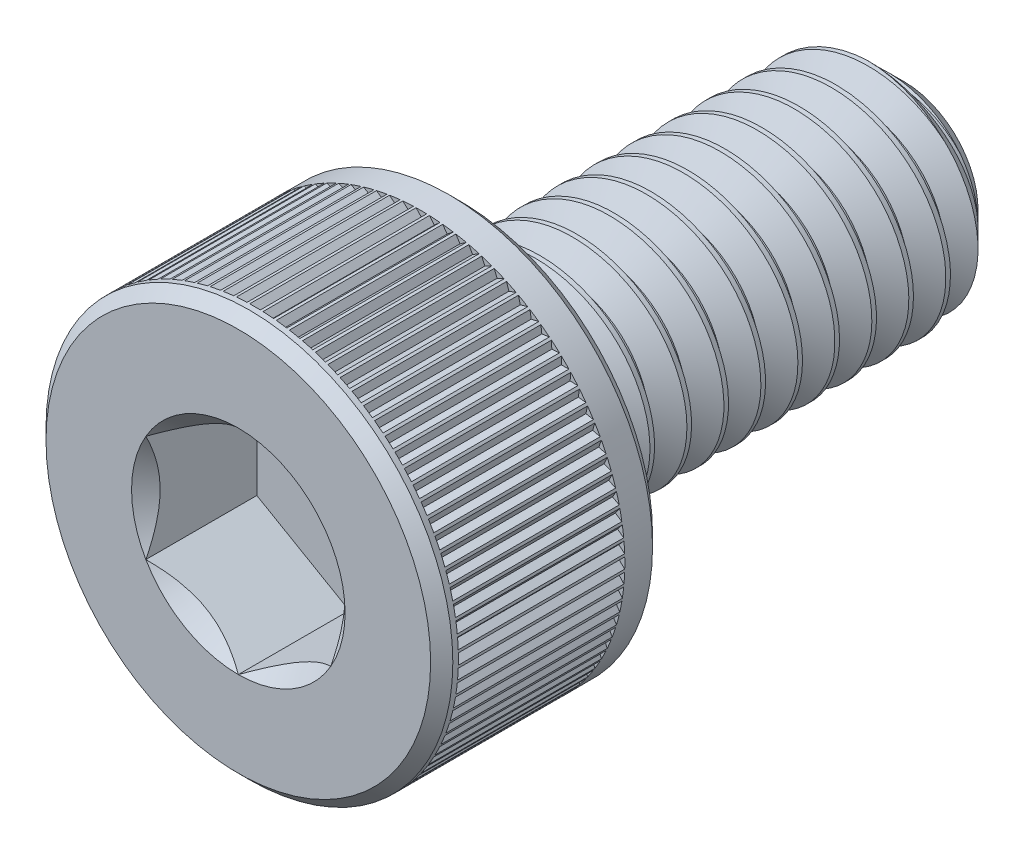
SolidWorks part; units mm, degrees
ref_plane "Front Plane" through (0, 0, 0) normal (0, 0, 1) x (1, 0, 0)
ref_plane "Top Plane" through (0, 0, 0) normal (0, 1, 0) x (1, 0, 0)
ref_plane "Right Plane" through (0, 0, 0) normal (1, 0, 0) x (0, 0, -1)
sketch "Sketch1" plane through (0, 0, 0) normal (1, 0, 0) x (0, 0, -1)
  line L0 (-4.5, 0) -> (4.5, 0) construction
  line L1 (4.5, 0) -> (4.5, 1) construction
  line L2 (4.5, 1) -> (4, 1.5) construction
  line L3 (4, 1.5) -> (-1.5, 1.5) construction
  line L5 (-1.5, 1.5) -> (-1.5, 2.75) construction
  line L6 (-1.5, 2.75) -> (-4.5, 2.75) construction
  line L7 (-4.5, 2.75) -> (-4.5, 0) construction
  line L8 (4.5, 1) -> (4.5, 1.5) construction
  line L9 (4.4687, 1.5541) -> (4.7187, 1.1211) construction
  line L10 (4.7187, 1.1211) -> (4.9687, 1.5541) construction
  line L11 (4.9687, 1.5541) -> (4.4687, 1.5541) construction
  line L12 (4.7188, 1.5541) -> (4.7188, 1.5) construction
  line L13 (4.7187, 1.1211) -> (4.7187, 1.1752) construction
  line L14 (4.6875, 1.1752) -> (4.75, 1.1752) construction
  line L15 (4.5, 1.5) -> (4.9375, 1.5) construction
  line L16 (4.4844, 1.5271) -> (4.9531, 1.5271) construction
  line L17 (4.5, 0) -> (4.5, -1.5) construction
  line L18 (-1.65, 2.75) -> (-1.5, 2.6) construction
  line L19 (-4.35, 2.75) -> (-4.5, 2.6) construction
  point P0 (-4.5, 1.25)
  point P3 (2.75, 1.5)
  point P4 (0, 0)
  point P22 (4.7187, 1.1752)
  point P24 (-1.5, 1.5)
  point P25 (4.7188, 1.5)
  point P28 (4.7188, 1.5271)
  point P29 (2.75, -1.5)
  point P31 (-3, 2.75)
  point P37 (-2.025, 2.75)
  point P38 (-4.275, 2.75)
  point P41 (-3, 0)
  dimension "head height" = 3
  dimension "D1" = 45
  dimension "Head Diameter" = 5.5
  dimension "Thread Size" = 3
  dimension "drive size" = 2.5
  dimension "Thread Pitch" = 0.5
  dimension "D2" = 0.0625
  dimension "D3" = 0.5
  dimension "D4" = 1.75
  dimension "D7" = 0.15
  dimension "D8" = 0.15
  dimension "D9" = 0.15
  dimension "D10" = 0.075
  dimension "D11" = 0.375
  dimension "length" = 6
  dimension "Drive Depth" = 1.5
sketch "Sketch2" plane through (0, 0, 0) normal (1, 0, 0) x (0, 0, -1)
  line L1 (-4.35, 2.75) -> (-1.65, 2.75)
  line L4 (4, 1.5) -> (4.5, 1)
  line L5 (4.5, 1) -> (4.5, 0)
  line L6 (-1.65, 2.75) -> (-1.5, 2.6) construction
  line L7 (4.5, 0) -> (-4.5, 0)
  line L8 (-4.35, 2.75) -> (-4.5, 2.6) construction
  line L9 (-1.65, 2.75) -> (-1.5, 2.6)
  line L10 (-4.35, 2.75) -> (-4.5, 2.6)
  line L11 (-4.5, 2.6) -> (-4.5, 0)
  line L12 (-1.5, 2.6) -> (-1.5, 1.5)
  line L13 (-1.5, 1.5) -> (4, 1.5)
revolve "Revolve1" add sketch "Sketch2" angle 360 about L7
sketch "Sketch3" plane through (0, 0, 4.5) normal (0, 0, 1) x (1, 0, 0)
  line L1 (0, 1.4434) -> (-1.25, 0.7217)
  line L2 (-1.25, 0.7217) -> (-1.25, -0.7217)
  line L3 (-1.25, -0.7217) -> (0, -1.4434)
  line L4 (0, -1.4434) -> (1.25, -0.7217)
  line L5 (1.25, -0.7217) -> (1.25, 0.7217)
  line L6 (1.25, 0.7217) -> (0, 1.4434)
  circle A0 centre (0, 0) radius 1.25 construction
  dimension "D1" = 2.5
extrude "Cut-Extrude1" cut sketch "Sketch3" against normal up to vertex (1.5 mm away) up to point (0, 0, 3)
sketch "Sketch4" plane through (0, 0, 4.5) normal (0, 0, 1) x (1, 0, 0)
  circle A0 centre (0, 0) radius 1.4434
extrude "Cut-Extrude2" cut sketch "Sketch4" against normal blind 0.5 draft 45
ref_plane "Plane1" through (0, 0, 1.5) normal (0, 0, 1) x (1, 0, 0)
split "Split1" bodies to split 106 resulting bodies 108 115 split by face at (-2.6, 0, 1.5)
sketch "Sketch6" plane through (0, 0, -4.5) normal (0, 0, -1) x (-1, 0, 0)
  circle A0 centre (0, 0) radius 1.5
curve "Helix/Spiral1" pitch 0.5 height 6.5 radius 1.5 centre (0, 0, -4.5) axis (0, 0, 1) start towards (0, 1, 0)
sketch "Sketch7" plane through (0, 0, 0) normal (1, 0, 0) x (0, 0, -1)
  line L0 (4.4844, 1.5271) -> (4.9531, 1.5271)
  line L1 (4.9531, 1.5271) -> (4.75, 1.1752)
  line L2 (4.75, 1.1752) -> (4.6875, 1.1752)
  line L3 (4.6875, 1.1752) -> (4.4844, 1.5271)
sweep "Cut-Sweep1" cut profiles "Sketch7" path "Helix/Spiral1" align with end faces yes
sketch "Sketch8" plane through (0, 0, 1.5) normal (0, 0, -1) x (-1, 0, 0)
  circle A0 centre (0, 0) radius 1.5
extrude "Boss-Extrude1" add sketch "Sketch8" along normal through all draft 45
ref_plane "Plane2" through (0, 0, 3) normal (0, 0, 1) x (1, 0, 0)
sketch "Sketch9" plane through (0, 0, 3) normal (0, 0, 1) x (1, 0, 0)
  line L0 (0, 2.6744) -> (0.072, 2.7491)
  line L1 (0, 2.6744) -> (-0.072, 2.7491)
  line L2 (0, 2.75) -> (0, 0) construction
  line L3 (-0.072, 2.7491) -> (0, 0) construction
  line L4 (0, 0) -> (0.072, 2.7491) construction
  arc A0 (0.072, 2.7491) -> (-0.072, 2.7491) centre (0, 0) ccw
  circle A1 centre (0, 0) radius 2.6744 construction
  dimension "D1" = 5.5
  dimension "D2" = 5.3487
  dimension "D3" = 3
extrude "Cut-Extrude4" cut sketch "Sketch9" against normal up to vertex (0.975 mm away) and the other way up to vertex (1.275 mm away) up to point (0, 2.75, 2.025) other way up to point (0, 2.75, 4.275)
pattern_circular "CirPattern2" count 96 over 360 about axis through (0, 0, 4.5) along (0, 0, -1) of "Cut-Extrude4"
equation "\"D2@Sketch1\" = \"Thread Pitch@Sketch1\" / 8"
equation "\"D3@Sketch1\" = \"Thread Pitch@Sketch1\""
equation "\"D3@Helix/Spiral1\" = \"length@Sketch1\" + \"Thread Pitch@Sketch1\""
equation "\"D4@Helix/Spiral1\" = \"Thread Pitch@Sketch1\""
equation "\"D4@Sketch1\" = \"Thread Pitch@Sketch1\" * 3.5"
equation "\"D7@Sketch1\"=\"head height@Sketch1\"*.05"
equation "\"D8@Sketch1\"=\"D7@Sketch1\""
equation "\"D9@Sketch1\"=\"D7@Sketch1\""
equation "\"D10@Sketch1\"=\"D7@Sketch1\"/2"
equation "\"D11@Sketch1\"=\"D10@Sketch1\"*5"
equation "\"D1@CirPattern2\"=( 360 / \"D3@Sketch9\" )*0.8"
equation "\"D1@Sketch3\" = \"drive size@Sketch1\""
equation "\"D2@Sketch9\"=\"Head Diameter@Sketch1\" * 0.9725"
